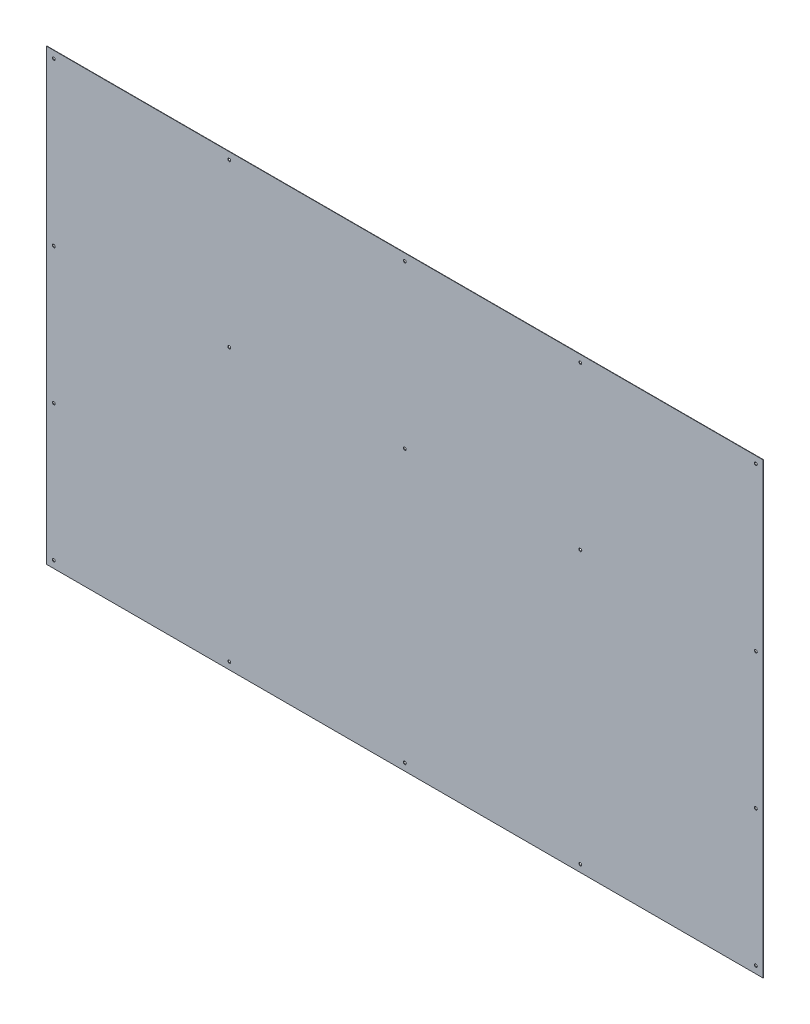
SolidWorks part; units mm, degrees
ref_plane "Front Plane" through (0, 0, 0) normal (0, 0, 1) x (1, 0, 0)
ref_plane "Top Plane" through (0, 0, 0) normal (0, 1, 0) x (1, 0, 0)
ref_plane "Right Plane" through (0, 0, 0) normal (1, 0, 0) x (0, 0, -1)
sketch "Sketch1" plane through (0, 0, 0) normal (0, 0, 1) x (1, 0, 0)
  line L0 (-980, 153.5) -> (-980, -606.5) construction
  line L1 (1000, 626.5) -> (-1000, 626.5)
  line L2 (1000, 626.5) -> (1000, -626.5)
  line L3 (1000, -626.5) -> (-1000, -626.5)
  line L4 (-1000, 626.5) -> (-1000, -626.5)
  line L5 (980, 153.5) -> (980, -606.5) construction
  line L8 (0, -606.5) -> (980, -606.5) construction
  line L11 (0, 606.5) -> (980, 606.5) construction
  circle A0 centre (-980, 606.5) radius 3
  circle A1 centre (980, 606.5) radius 3
  circle A2 centre (0, 606.5) radius 3
  circle A3 centre (-980, -606.5) radius 3
  circle A4 centre (980, -606.5) radius 3
  circle A5 centre (0, -606.5) radius 3
  circle A8 centre (-490, -606.5) radius 3
  circle A9 centre (490, -606.5) radius 3
  circle A10 centre (-490, 606.5) radius 3
  circle A11 centre (490, 606.5) radius 3
  circle A12 centre (980, 153.5) radius 3
  circle A13 centre (490, 153.5) radius 3
  circle A14 centre (0, 153.5) radius 3
  circle A15 centre (-490, 153.5) radius 3
  circle A16 centre (-980, 153.5) radius 3
  circle A17 centre (980, -226.5) radius 3
  circle A18 centre (-980, -226.5) radius 3
  point P0 (0, 0)
  dimension "D4" = 6
  dimension "D5" = 6
  dimension "D6" = 6
  dimension "D7" = 6
  dimension "D8" = 6
  dimension "D9" = 6
  dimension "D10" = 6
  dimension "D11" = 6
  dimension "D12" = 853
  dimension "D13" = 6
  dimension "D14" = 6
  dimension "D3" = 473
  dimension "D1" = 1253
  dimension "D2" = 2000
  dimension "D15" = 2
extrude "Boss-Extrude1" add sketch "Sketch1" along normal blind 1
chamfer "Chamfer1" distance 1 angle 45 17 edges at (-977, 153.5, 1) (-977, -226.5, 1) (-977, -606.5, 1) (-487, -606.5, 1) (3, -606.5, 1) (493, -606.5, 1) (983, -606.5, 1) (983, -226.5, 1) (983, 153.5, 1) (983, 606.5, 1) (493, 606.5, 1) (3, 606.5, 1) (-487, 606.5, 1) (-977, 606.5, 1) (493, 153.5, 1) (3, 153.5, 1) (-487, 153.5, 1)
